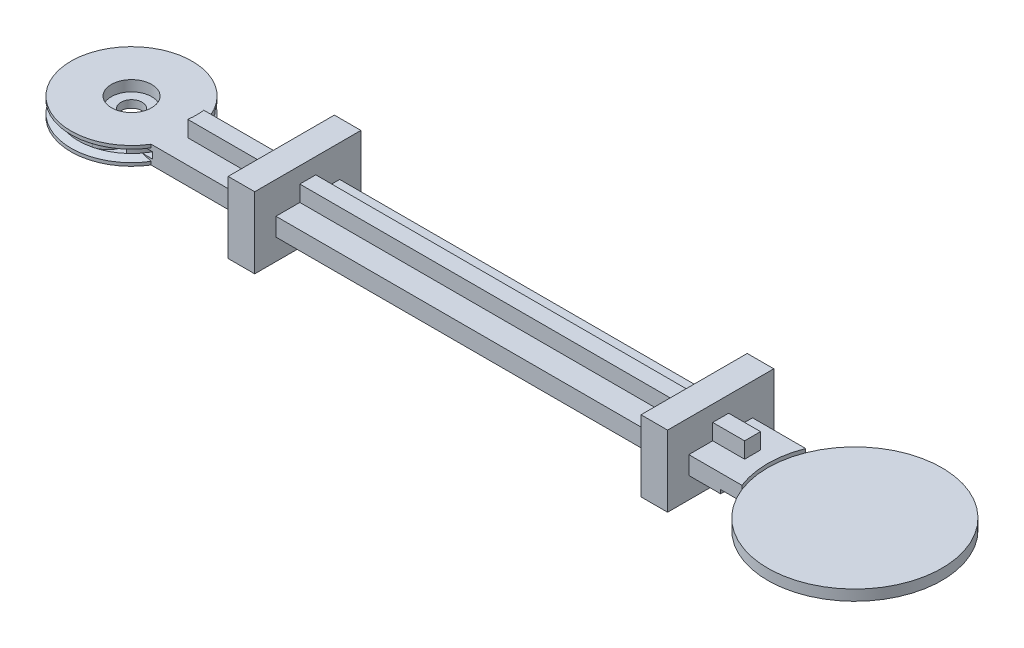
SolidWorks part; units mm, degrees
note: The reader was unsure of these and kept them because the rebuilt part matched: shared geometry of "Sketch6<3>".
ref_plane "Front Plane" through (0, 0, 0) normal (0, 0, 1) x (1, 0, 0)
ref_plane "Top Plane" through (0, 0, 0) normal (0, 1, 0) x (1, 0, 0)
ref_plane "Right Plane" through (0, 0, 0) normal (1, 0, 0) x (0, 0, -1)
sketch "Sketch1" plane through (0, 0, 0) normal (0, 1, 0) x (1, 0, 0)
  circle A0 centre (0, 0) radius 5
  dimension "D1" = 10
extrude "Boss-Extrude1" add sketch "Sketch1" along normal blind 1.7
sketch "Sketch2" plane through (0, 0, 0) normal (0, 0, 1) x (1, 0, 0)
  line L0 (5, 0) -> (5, 1.7) construction
  line L1 (5, 0) -> (5, 1.7)
  line L2 (5, 1.7) -> (5.7, 1.7)
  line L3 (5.7, 1.7) -> (5.7, 1.4)
  line L4 (5.7, 1.4) -> (5, 1.15)
  line L5 (5, 0.85) -> (5.4316, 0.85) construction
  line L6 (5.7, 0.3) -> (5, 0.55)
  line L7 (5.7, 0) -> (5.7, 0.3)
  line L8 (5, 0) -> (5.7, 0)
  dimension "D3" = 0.7
revolve "Revolve1" add sketch "Sketch2" angle 360 about axis through (0, 1.7, 0) along (0, -1, 0)
ref_plane "Plane1" through (0, 0.55, 0) normal (0, 1, 0) x (1, 0, 0)
sketch "Sketch3" plane through (0, 0.55, 0) normal (0, 1, 0) x (1, 0, 0)
  line L0 (3, -4) -> (3, 4) construction
  line L1 (3.3, -3.7563) -> (3.3, 3.7563)
  line L2 (2.7, -2.9172) -> (2.7, 2.9172)
  line L3 (0, 0) -> (1.2394, 0) construction
  line L4 (3.3, -4) -> (3.3, 4) construction
  line L6 (2.7, -4) -> (2.7, 4) construction
  circle A2 centre (0, 0) radius 5 construction
  circle A3 centre (0, 0) radius 5
  arc A4 (2.7, 2.9172) -> (1.1667, 4.862) centre (0.7, 2.9172) ccw
  arc A5 (2.7, -2.9172) -> (1.1667, -4.862) centre (0.7, -2.9172) cw
  dimension "D4" = 2
extrude "EP_CableSlot" cut sketch "Sketch3" along normal blind 0.6 contours L2 A5 A3 L1 A4
sketch "Sketch4" plane through (0, 1.7, 0) normal (0, 1, 0) x (1, 0, 0)
  circle A0 centre (0, 0) radius 1.9
  dimension "D1" = 3.8
extrude "EP_BallBearingSlot" cut sketch "Sketch4" against normal blind 1
sketch "Sketch5" plane through (0, 0.7, 0) normal (0, 1, 0) x (1, 0, 0)
  circle A0 centre (0, 0) radius 1.9 construction
  circle A1 centre (0, 0) radius 1.9 construction
  circle A2 centre (0, 0) radius 1
extrude "EP_ShaftHole" cut sketch "Sketch5" against normal up to surface (0.7 mm away) up to face at (0, 0, 5.7)
ref_plane "Plane2" through (0, 0.85, 0) normal (0, 1, 0) x (1, 0, 0)
sketch "Sketch6" plane through (0, 0.85, 0) normal (0, 1, 0) x (1, 0, 0)
  line L0 (0, 0) -> (68.1, 0) construction
  line L1 (4, -3) -> (60.4685, -3)
  line L2 (4, 3) -> (60.4685, 3)
  line L3 (0, 0) -> (68.1, 0) construction
  line L4 (0, 3) -> (68.1, 3) construction
  line L5 (0, -3) -> (68.1, -3) construction
  circle A2 centre (68.1, 0) radius 8.2
  arc A3 (3.3, 3.7563) -> (1.1667, 4.862) centre (0, 0) ccw construction
  arc A4 (1.1667, 4.862) -> (1.1667, -4.862) centre (0, 0) ccw construction
  arc A5 (1.1667, -4.862) -> (3.3, -3.7563) centre (0, 0) ccw construction
  arc A6 (3.3, -3.7563) -> (3.3, 3.7563) centre (0, 0) ccw construction
  arc A7 (3.3, 3.7563) -> (1.1667, 4.862) centre (0, 0) ccw
  arc A8 (1.1667, 4.862) -> (1.1667, -4.862) centre (0, 0) ccw
  arc A9 (1.1667, -4.862) -> (3.3, -3.7563) centre (0, 0) ccw
  arc A10 (3.3, -3.7563) -> (3.3, 3.7563) centre (0, 0) ccw
  dimension "D2" = 16.4
  dimension "D1" = 68.1
  dimension "D3" = 3
  dimension "D4" = 3
extrude "Boss-Extrude2" add sketch "Sketch6" along normal up to surface (1.7 mm away) from surface at -0.85
sketch "Sketch8" plane through (0, 1.7, 0) normal (0, 1, 0) x (1, 0, 0)
  line L0 (5.4991, 1.5) -> (11.4991, 1.5)
  line L1 (4.8466, 3) -> (60.4685, 3) construction
  line L2 (4.8466, 3) -> (14.0972, 3)
  arc A0 (4.8466, 3) -> (4.8466, -3) centre (0, 0) ccw construction
  arc A1 (4.8466, 3) -> (4.8466, -3) centre (0, 0) ccw construction
  arc A2 (4.8466, 3) -> (4.8466, -3) centre (0, 0) cw
  arc A3 (11.4991, 1.5) -> (14.0972, 3) centre (11.4991, 4.5) ccw
  line M6 (60.4685, 3) -> (4.8466, 3)
  dimension "D3" = 3
  dimension "D1" = 6
  dimension "D2" = 1.5
extrude "HumerusClearanceCut" cut sketch "Sketch8" against normal up to surface (1.7 mm away) contours L0 A3 A2 M6 up to face at (0, 0, 1)
sketch "Sketch11" plane through (0, 0.55, 0) normal (0, 1, 0) x (1, 0, 0)
  line L0 (5.4991, 1.5) -> (8.9991, 1.5)
  line L1 (8.9991, 1.5) -> (4.2445, -3.8045)
  line L2 (4.8466, 3) -> (4, 3) construction
  line L3 (4, -3) -> (4.8466, -3) construction
  line L4 (4.8466, 3) -> (4, 3)
  line L5 (4, -3) -> (4.8466, -3)
  arc A0 (5.4991, 1.5) -> (4.8466, -3) centre (0, 0) ccw construction
  arc A1 (5.4991, 1.5) -> (4.8466, -3) centre (0, 0) ccw
  arc A2 (5.4991, 1.5) -> (4.8466, -3) centre (0, 0) cw
  arc A3 (3.3, 3.7563) -> (1.1667, 4.862) centre (0, 0) ccw construction
  arc A4 (4, 3) -> (3.3, 3.7563) centre (0, 0) ccw construction
  arc A5 (1.1667, 4.862) -> (1.1667, -4.862) centre (0, 0) ccw construction
  arc A6 (1.1667, -4.862) -> (3.3, -3.7563) centre (0, 0) ccw construction
  arc A7 (3.3, -3.7563) -> (4, -3) centre (0, 0) ccw construction
  arc A8 (3.3, 3.7563) -> (1.1667, 4.862) centre (0, 0) ccw
  arc A9 (4, 3) -> (3.3, 3.7563) centre (0, 0) ccw
  arc A10 (1.1667, 4.862) -> (1.1667, -4.862) centre (0, 0) ccw
  arc A11 (1.1667, -4.862) -> (3.3, -3.7563) centre (0, 0) ccw
  arc A12 (3.3, -3.7563) -> (4, -3) centre (0, 0) ccw
  arc A13 (4, 3) -> (4, -3) centre (0, 0) cw
  dimension "D1" = 3.5
extrude "CableClearanceCut" cut sketch "Sketch11" along normal up to surface (0.6 mm away) contours L0 A2 A1 L1 | L4 A13 L5 A2 A1 up to face at (2.5238, 1.15, 0)
extrude "MainPlate" add sketch "Sketch6<3>" along normal mid plane 1 contours A2
sketch "Sketch6<3>" plane through (0, 0.85, 0) normal (0, 1, 0) x (1, 0, 0) same geometry as "Sketch6"
sketch "Sketch12" plane through (0, 0, 0) normal (0, 1, 0) x (1, 0, 0)
  line L0 (60.4685, 3) -> (58.4685, 3)
  line L1 (14.0972, 3) -> (60.4685, 3) construction
  line L2 (58.4685, 3) -> (58.4685, -3)
  line L3 (4.8466, -3) -> (60.4685, -3) construction
  line L4 (58.4685, -3) -> (60.4685, -3)
  arc A0 (60.4685, -3) -> (60.4685, 3) centre (68.1, 0) ccw construction
  arc A1 (60.4685, -3) -> (60.4685, 3) centre (68.1, 0) ccw construction
  arc A2 (60.4685, -3) -> (60.4685, 3) centre (68.1, 0) cw
  line M11 (14.0972, 3) -> (60.4685, 3)
  arc M12 (60.4685, 3) -> (60.4685, -3) centre (68.1, 0) ccw
  line M13 (60.4685, -3) -> (4.8466, -3)
  dimension "D1" = 2
extrude "FingerPulleyClearanceCut" cut sketch "Sketch12" along normal up to surface (0.35 mm away) contours L2 M11 M12 M13 up to face at (68.1, 0.35, 0)
sketch "Sketch10" plane through (0, 1.7, 0) normal (0, 1, 0) x (1, 0, 0)
  line L0 (14.0972, 3) -> (14.0972, -3) construction
  line L1 (4.8466, -3) -> (60.4685, -3) construction
  line L2 (14.0972, 0) -> (16.5972, 0) construction
  line L4 (14.0972, 5) -> (16.5972, 5)
  line L5 (14.0972, 5) -> (14.0972, -5)
  line L6 (14.0972, -5) -> (16.5972, -5)
  line L7 (16.5972, 5) -> (16.5972, -5)
  line L8 (15.3472, -5) -> (15.3472, 5) construction
  line L9 (14.0972, 0) -> (16.5972, 0) construction
  point P8 (15.3472, 0)
  dimension "D1" = 2.5
  dimension "D2" = 2.5
  dimension "D3" = 2
extrude "Block1" add sketch "Sketch10" along normal blind 3 and the other way offset from surface (3.7 mm away) 2
sketch "Sketch13" plane through (0, 1.7, 0) normal (0, 1, 0) x (1, 0, 0)
  line L0 (54.2185, 3) -> (54.2185, -3) construction
  line L1 (16.5972, 3) -> (60.4685, 3) construction
  line L2 (16.5972, -3) -> (60.4685, -3) construction
  line L4 (52.9685, 5) -> (55.4685, 5)
  line L5 (52.9685, 5) -> (52.9685, -5)
  line L6 (52.9685, -5) -> (55.4685, -5)
  line L7 (55.4685, 5) -> (55.4685, -5)
  line L8 (54.2185, -5) -> (54.2185, 5) construction
  line L9 (52.9685, 0) -> (55.4685, 0) construction
  point P6 (54.2185, 0)
  dimension "D1" = 2.5
  dimension "D3" = 5
extrude "Block2" add sketch "Sketch13" along normal blind 3 and the other way offset from surface (3.7 mm away) 2 other way up to face at (37.5328, 0, 0)
sketch "Sketch14" plane through (0, 1.7, 0) normal (0, 1, 0) x (1, 0, 0)
  line L2 (58.4685, 0) -> (6.1, 0) construction
  line L3 (58.4685, 0.75) -> (6.0537, 0.75)
  line L4 (58.4685, -0.75) -> (6.0537, -0.75)
  line L5 (58.4685, 3) -> (58.4685, -3) construction
  line L6 (58.4685, 3) -> (58.4685, -3)
  line L7 (5.4991, 1.5) -> (11.4991, 1.5) construction
  line L8 (4.8466, -3) -> (14.0972, -3) construction
  line L9 (58.4685, 0.75) -> (6.1, 0.75) construction
  line L10 (58.4685, -0.75) -> (6.1, -0.75) construction
  arc A0 (5.4991, 1.5) -> (4.8466, -3) centre (0, 0) ccw construction
  arc A1 (5.4991, 1.5) -> (4.8466, -3) centre (0, 0) ccw construction
  arc A2 (5.4991, 1.5) -> (4.8466, -3) centre (0, 0) cw construction
  arc A3 (5.9127, 1.5) -> (5.3113, -3) centre (0, 0) cw
  line M3 (52.9685, -3) -> (52.9685, 3)
  line M5 (16.5972, 3) -> (16.5972, -3)
  dimension "D1" = 0.4
  dimension "D2" = 0.75
  dimension "D3" = 0.75
extrude "StiffenerRib" add sketch "Sketch14" along normal blind 1.5 and the other way offset from surface (3.2 mm away) 1.5 contours L3 A3 L4 M5 | L4 L3 M3 M5 | L6 L3 L4 M3 other way up to face at (34.7828, 0, 0)
equation "\"Bolt1_D\"=2mm"
equation "\"Bolt1_HeadD\"=3.2mm"
equation "\"Bolt1_NutD\"=3.9mm"
equation "\"Bolt2_D\"=1.6mm"
equation "\"Bolt2_HeadD\"=2.9mm"
equation "\"Bolt2_HeadThickness\"=1mm"
equation "\"Bolt2_NutD\"=2.5mm"
equation "\"Bolt2_NutThickness\"=1.4mm"
equation "\"Screw1_D\"=1.2mm"
equation "\"Screw1_HeadD\"=2mm"
equation "\"Tube1_InnerD\"=0.8mm"
equation "\"Tube1_OuterD\"=1.2mm"
equation "\"Tube2_InnerD\"=0.3mm"
equation "\"Tube2_OuterD\"=0.8mm"
equation "\"TubeClipW\"=1.5mm"
equation "\"TubeClipH_Tube1\"=1.5mm"
equation "\"TubeClipH_Tube2\"=1.1mm"
equation "\"TubeClipLock_SideL\"=1.5mm"
equation "\"TubeClipLock_W\"=0.7mm"
equation "\"Pulley_GrooveDepth\"=0.7mm"
equation "\"Cable_D\"=0.3mm"
equation "\"BallBearing1_InnerD\"=2mm"
equation "\"BallBearing1_OuterD\"=4mm"
equation "\"BallBearing1_Thickness\"=2mm"
equation "\"BallBearing2_InnerD\"=1.5mm"
equation "\"BallBearing2_OuterD\"=4mm"
equation "\"BallBearing2_Thickness\"=1.2mm"
equation "\"BallBearing3_InnerD\"=1mm"
equation "\"BallBearing3_OuterD\"=3mm"
equation "\"BallBearing3_Thickness\"=1mm"
equation "\"HumerusL\"=37.2mm"
equation "\"HumerusElbowSidePulleyD\"=10mm"
equation "\"RadiusL\"=68.1mm"
equation "\"ElbowExtendedAngle\"=140deg"
equation "\"ElbowFlexedAngle\"=38deg"
equation "\"Digit5ExtendedAngle\"=80deg"
equation "\"Digit5FlexedAngle\"=24deg"
equation "\"Digit4ExtendedAngle\"=108deg"
equation "\"Digit4FlexedAngle\"=34deg"
equation "\"Digit3ExtendedAngle\"=145deg"
equation "\"Digit3FlexedAngle\"=44deg"
equation "\"KST_Servo_ShaftBolt_D\"=2.5mm"
equation "\"KST_Servo_ShaftBolt_HeadD\"=5.2mm"
equation "\"XL330_M077_T_HornScrew_D\"=1.9mm"
equation "\"XL330_M077_T_HornScrew_HeadD\"=3.3mm"
equation "\"D1@Sketch1\"=\"HumerusElbowSidePulleyD\""
equation "\"D1@Sketch2\"=\"Cable_D\""
equation "\"D3@Sketch2\"=\"Pulley_GrooveDepth\""
equation "\"D1@Sketch3\"=\"BallBearing2_OuterD\"/2 + 1"
equation "\"D1@EP_CableSlot\"=\"Cable_D\"*2"
equation "\"D1@Sketch4\"=\"BallBearing2_OuterD\" - 0.2"
equation "\"D1@EP_BallBearingSlot\"=\"BallBearing2_Thickness\"-0.2"
equation "\"D1@Sketch5\"=\"BallBearing2_InnerD\" + 0.5"
equation "\"D1@Sketch6\"=\"RadiusL\""
equation "\"D2@Sketch6\"=15 + 2*\"Pulley_GrooveDepth\""
equation "\"D2@Sketch10\"=\"D1@Sketch10\""
equation "\"D3@Sketch10\"=\"Screw1_D\" + 0.8"
equation "\"D2@Sketch13\"=\"Screw1_D\" + 0.8"
